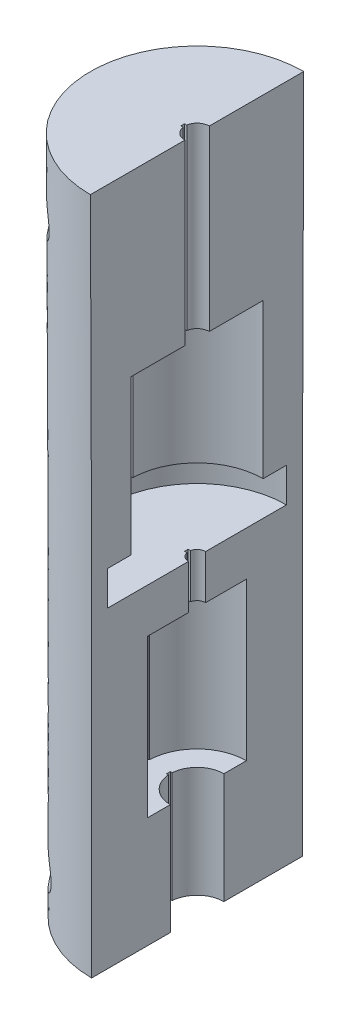
SolidWorks part; units mm, degrees
ref_plane "Front Plane" through (0, 0, 0) normal (0, 0, 1) x (1, 0, 0)
ref_plane "Top Plane" through (0, 0, 0) normal (0, 1, 0) x (1, 0, 0)
ref_plane "Right Plane" through (0, 0, 0) normal (1, 0, 0) x (0, 0, -1)
sketch "Sketch1" plane through (0, 0, 0) normal (0, 1, 0) x (1, 0, 0)
  line L0 (0, 14.75) -> (0, 17.2355)
  circle A0 centre (0, 0) radius 14.75
  dimension "D1" = 29.5
ref_plane "Plane1" through (0, 95, 0) normal (0, 1, 0) x (1, 0, 0)
sketch "Sketch2" plane through (0, 95, 0) normal (0, 1, 0) x (1, 0, 0)
  line L0 (0, 14.925) -> (0, 17.0241)
  circle A0 centre (0, 0) radius 14.925
  dimension "D1" = 29.85
loft "Loft1" add section "Sketch1" section "Sketch2" connector at (-4.3814, 0, -14.0843) connector at (-7.1655, 95, -13.0924)
sketch "Sketch3" plane through (0, 0, 0) normal (0, 1, 0) x (1, 0, 0)
  line L1 (0, 14.925) -> (21.9934, 14.925)
  line L2 (0, 14.925) -> (0, -15.2778)
  line L3 (0, -15.2778) -> (21.9934, -15.2778)
  line L4 (21.9934, 14.925) -> (21.9934, -15.2778)
  circle A0 centre (0, 0) radius 14.925 construction
extrude "Cut-Extrude1" cut sketch "Sketch3" along normal blind 100
sketch "Sketch4" plane through (0, 0, 0) normal (1, 0, 0) x (0, 0, -1)
  line L0 (0, 0) -> (0, 95)
  line L1 (17.1781, 95) -> (-17.1781, 95) construction
sketch "Sketch5" plane through (0, 0, 0) normal (0, 1, 0) x (1, 0, 0)
  circle A0 centre (0, 0) radius 3.75
  dimension "D1" = 7.5
extrude "Cut-Extrude4" cut sketch "Sketch5" along normal blind 15.5
ref_plane "Plane2" through (0, 15.5, 0) normal (0, -1, 0) x (-1, 0, 0)
sketch "Sketch6" plane through (0, 15.5, 0) normal (0, -1, 0) x (-1, 0, 0)
  circle A0 centre (0, 0) radius 6.9
  dimension "D1" = 13.8
extrude "Cut-Extrude5" cut sketch "Sketch6" against normal blind 22
ref_plane "Plane3" through (0, 37.5, 0) normal (0, -1, 0) x (-1, 0, 0)
sketch "Sketch7" plane through (0, 37.5, 0) normal (0, -1, 0) x (-1, 0, 0)
  line L0 (0, -6.9) -> (0, 6.9) construction
  circle A0 centre (0, 0) radius 1.2
  dimension "D1" = 2.4
extrude "Cut-Extrude6" cut sketch "Sketch7" against normal blind 6.2
ref_plane "Plane4" through (0, 43.7, 0) normal (0, -1, 0) x (-1, 0, 0)
sketch "Sketch8" plane through (0, 43.7, 0) normal (0, -1, 0) x (-1, 0, 0)
  line L0 (0, -1.2) -> (0, 1.2) construction
  circle A0 centre (0, 0) radius 12.5
  dimension "D1" = 25
extrude "Cut-Extrude7" cut sketch "Sketch8" against normal blind 4.8
ref_plane "Plane5" through (0, 48.5, 0) normal (0, -1, 0) x (-1, 0, 0)
sketch "Sketch9" plane through (0, 48.5, 0) normal (0, -1, 0) x (-1, 0, 0)
  circle A0 centre (0, 0) radius 9.25
  dimension "D1" = 18.5
extrude "Cut-Extrude8" cut sketch "Sketch9" against normal blind 21.6
sketch "Sketch10" plane through (0, 95, 0) normal (0, 1, 0) x (1, 0, 0)
  circle A0 centre (0, 0) radius 1.71
  dimension "D1" = 3.42
extrude "Cut-Extrude9" cut sketch "Sketch10" against normal blind 40
sketch "Sketch12" plane through (0, 0, 0) normal (1, 0, 0) x (0, 0, -1)
  line L0 (-0.25, 95) -> (0.25, 95)
  line L1 (10.8008, 95) -> (-10.8008, 95) construction
  line L2 (-1.71, 70.1) -> (1.71, 70.1) construction
  line L3 (-0.25, 95) -> (0.25, 95)
  line L4 (-0.25, 95) -> (-0.25, 70.1)
  line L5 (-0.25, 70.1) -> (0.25, 70.1)
  line L6 (0.25, 95) -> (0.25, 70.1)
  point P6 (0, 95)
  dimension "D1" = 0.5
extrude "Cut-Extrude10" cut sketch "Sketch12" against normal blind 2 contours L6 L0 L4 L5 region at (0, 82.55, 0)
sketch "Sketch13" plane through (0, 0, 0) normal (1, 0, 0) x (0, 0, -1)
  line L0 (-0.25, 70.1) -> (0.25, 70.1)
  line L1 (-9.25, 70.1) -> (9.25, 70.1) construction
  line L2 (-0.25, 70.1) -> (0.25, 70.1) construction
  line L3 (0.25, 70.1) -> (0.25, 48.5)
  line L4 (-6.875, 48.5) -> (6.875, 48.5) construction
  line L5 (0.25, 48.5) -> (-0.25, 48.5)
  line L6 (-0.25, 48.5) -> (-0.25, 70.1)
extrude "Cut-Extrude11" cut sketch "Sketch13" against normal blind 10
sketch "Sketch14" plane through (0, 0, 0) normal (1, 0, 0) x (0, 0, -1)
  line L0 (0.25, 48.5) -> (-0.25, 48.5)
  line L1 (-6.875, 48.5) -> (6.875, 48.5) construction
  line L2 (0.25, 48.5) -> (0.25, 70.1) construction
  line L3 (-0.25, 48.5) -> (-0.25, 70.1) construction
  line L4 (-0.25, 48.5) -> (-0.25, 43.7)
  line L5 (-55, 43.7) -> (55, 43.7) construction
  line L6 (-0.25, 43.7) -> (0.25, 43.7)
  line L7 (0.25, 43.7) -> (0.25, 48.5)
extrude "Cut-Extrude12" cut sketch "Sketch14" against normal blind 12.5
sketch "Sketch15" plane through (0, 0, 0) normal (1, 0, 0) x (0, 0, -1)
  line L0 (-0.25, 43.7) -> (0.25, 43.7)
  line L1 (-55, 43.7) -> (55, 43.7) construction
  line L2 (-0.25, 48.5) -> (-0.25, 43.7) construction
  line L3 (0.25, 43.7) -> (0.25, 48.5) construction
  line L4 (0.25, 43.7) -> (0.25, 37.5)
  line L5 (-3.85, 37.5) -> (3.85, 37.5) construction
  line L6 (0.25, 37.5) -> (-0.25, 37.5)
  line L7 (-0.25, 37.5) -> (-0.25, 43.7)
extrude "Cut-Extrude13" cut sketch "Sketch15" against normal blind 1.5
sketch "Sketch16" plane through (0, 0, 0) normal (1, 0, 0) x (0, 0, -1)
  line L0 (-0.25, 37.5) -> (0.2502, 37.5)
  line L2 (-3.85, 37.5) -> (3.85, 37.5) construction
  line L3 (-0.25, 37.5) -> (-0.25, 43.7) construction
  line L4 (0.2502, 37.5) -> (0.2502, 15.5)
  line L5 (-55, 15.5) -> (55, 15.5) construction
  line L6 (0.2502, 15.5) -> (-0.25, 15.5)
  line L7 (-0.25, 15.5) -> (-0.25, 37.5)
extrude "Cut-Extrude14" cut sketch "Sketch16" against normal blind 7
sketch "Sketch17" plane through (0, 0, 0) normal (1, 0, 0) x (0, 0, -1)
  line L0 (0.2502, 15.5) -> (-0.2554, 15.5)
  line L1 (-55, 15.5) -> (55, 15.5) construction
  line L2 (0.2502, 37.5) -> (0.2502, 15.5) construction
  line L3 (-0.2554, 15.5) -> (-0.2554, 0)
  line L4 (-3.75, 0) -> (3.75, 0) construction
  line L5 (-0.2554, 0) -> (0.2502, 0)
  line L6 (0.2502, 0) -> (0.2502, 15.5)
extrude "Cut-Extrude15" cut sketch "Sketch17" against normal blind 4
sketch "Sketch18" plane through (0, 0, 0) normal (1, 0, 0) x (0, 0, -1)
  circle A0 centre (-9.3262, 6.1245) radius 3
  circle A1 centre (-9.25, 84.904) radius 3
  circle A2 centre (9.3262, 6.1245) radius 3
  circle A3 centre (9.25, 84.904) radius 3
  dimension "D1" = 6
  dimension "D2" = 6
extrude "Cut-Extrude16" cut sketch "Sketch18" against normal blind 15 from offset 1 offset against normal yes
